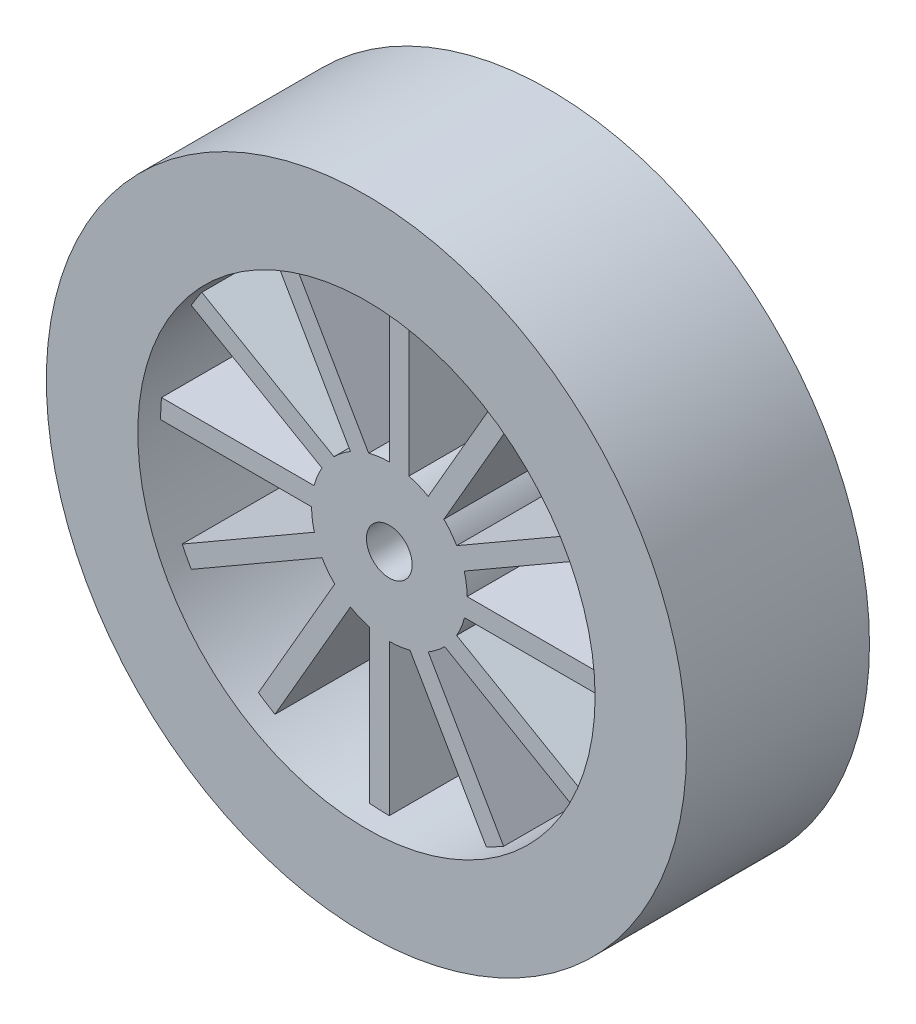
SolidWorks part; units mm, degrees
ref_plane "Front Plane" through (0, 0, 0) normal (0, 0, 1) x (1, 0, 0)
ref_plane "Top Plane" through (0, 0, 0) normal (0, 1, 0) x (1, 0, 0)
ref_plane "Right Plane" through (0, 0, 0) normal (1, 0, 0) x (0, 0, -1)
sketch "Sketch1" plane through (0, 0, 0) normal (0, 0, 1) x (1, 0, 0)
  line L0 (-8.5, 0) -> (-25, 0)
  line L1 (-8.2258, 2.1415) -> (-24.9081, 2.1415)
  line L2 (-7.3612, 4.25) -> (-21.6506, 12.5)
  line L3 (-6.053, 5.9675) -> (-20.5003, 14.3086)
  line L4 (-4.25, 7.3612) -> (-12.5, 21.6506)
  line L5 (-2.2583, 8.1945) -> (-10.5995, 22.6418)
  line L6 (0, 8.5) -> (0, 25)
  line L7 (2.1415, 8.2258) -> (2.1415, 24.9081)
  line L8 (4.25, 7.3612) -> (12.5, 21.6506)
  line L9 (5.9675, 6.053) -> (14.3086, 20.5003)
  line L10 (7.3612, 4.25) -> (21.6506, 12.5)
  line L11 (8.1945, 2.2583) -> (22.6418, 10.5995)
  line L12 (8.5, 0) -> (25, 0)
  line L13 (8.2258, -2.1415) -> (24.9081, -2.1415)
  line L14 (7.3612, -4.25) -> (21.6506, -12.5)
  line L15 (6.053, -5.9675) -> (20.5003, -14.3086)
  line L16 (4.25, -7.3612) -> (12.5, -21.6506)
  line L17 (2.2583, -8.1945) -> (10.5995, -22.6418)
  line L18 (0, -8.5) -> (0, -25)
  line L19 (-2.1415, -8.2258) -> (-2.1415, -24.9081)
  line L20 (-4.25, -7.3612) -> (-12.5, -21.6506)
  line L21 (-5.9675, -6.053) -> (-14.3086, -20.5003)
  line L22 (-7.3612, -4.25) -> (-21.6506, -12.5)
  line L23 (-8.1945, -2.2583) -> (-22.6418, -10.5995)
  circle A0 centre (0, 0) radius 35
  circle A1 centre (0, 0) radius 25
  circle A2 centre (0, 0) radius 7.5
  circle A3 centre (0, 0) radius 2.5
  circle A4 centre (0, 0) radius 8.5
  circle A5 centre (0, 0) radius 27
  point P56 (0, 0)
  dimension "D1" = 70
  dimension "D2" = 50
  dimension "D3" = 5
  dimension "D4" = 15
  dimension "D6" = 17
  dimension "D7" = 2
  dimension "D5" = 12
extrude "Boss-Extrude1" add sketch "Sketch1" along normal mid plane 15 contours A2 L5 A1 L4 | A2 L7 A1 L6 | A2 L9 A1 L8 | A2 L11 A1 L10 | A2 L13 A1 L12 | A2 L15 A1 L14 | A2 L17 A1 L16 | A2 L19 A1 L18 | A2 L21 A1 L20 | A2 L23 A1 L22 | A2 L3 A1 L2 | A2 L1 A1 L0 region at (-16.6891, 1.0727, 0) region at (-14.9895, -7.4156, 0) region at (-13.9169, 9.2735, 0) region at (-9.2735, -13.9169, 0) region at (-7.4156, 14.9895, 0) region at (-1.0727, -16.6891, 0) region at (1.0727, 16.6891, 0) region at (7.4156, -14.9895, 0) region at (9.2735, 13.9169, 0) region at (13.9169, -9.2735, 0) region at (14.9895, 7.4156, 0) region at (16.6891, -1.0727, 0)
extrude "Boss-Extrude2" add sketch "Sketch1<3>" along normal mid plane 20 contours A5 A1 region at (-26.2363, 0, 0)
sketch "Sketch1<3>" plane through (0, 0, 0) normal (0, 0, 1) x (1, 0, 0) same geometry as "Sketch1"
extrude "Boss-Extrude3" add sketch "Sketch1<4>" along normal mid plane 15 contours A4 A2 region at (-8.1927, 1.0489, 0)
sketch "Sketch1<4>" plane through (0, 0, 0) normal (0, 0, 1) x (1, 0, 0) same geometry as "Sketch1"
extrude "Boss-Extrude4" add sketch "Sketch1<5>" along normal mid plane 20 contours A0 A5 region at (-34.0101, 0, 0)
sketch "Sketch1<5>" plane through (0, 0, 0) normal (0, 0, 1) x (1, 0, 0) same geometry as "Sketch1"
extrude "Boss-Extrude5" add sketch "Sketch1<6>" along normal blind 7.5 contours A2 A3 region at (-7.2879, 0, 0)
sketch "Sketch1<6>" plane through (0, 0, 0) normal (0, 0, 1) x (1, 0, 0) same geometry as "Sketch1"
